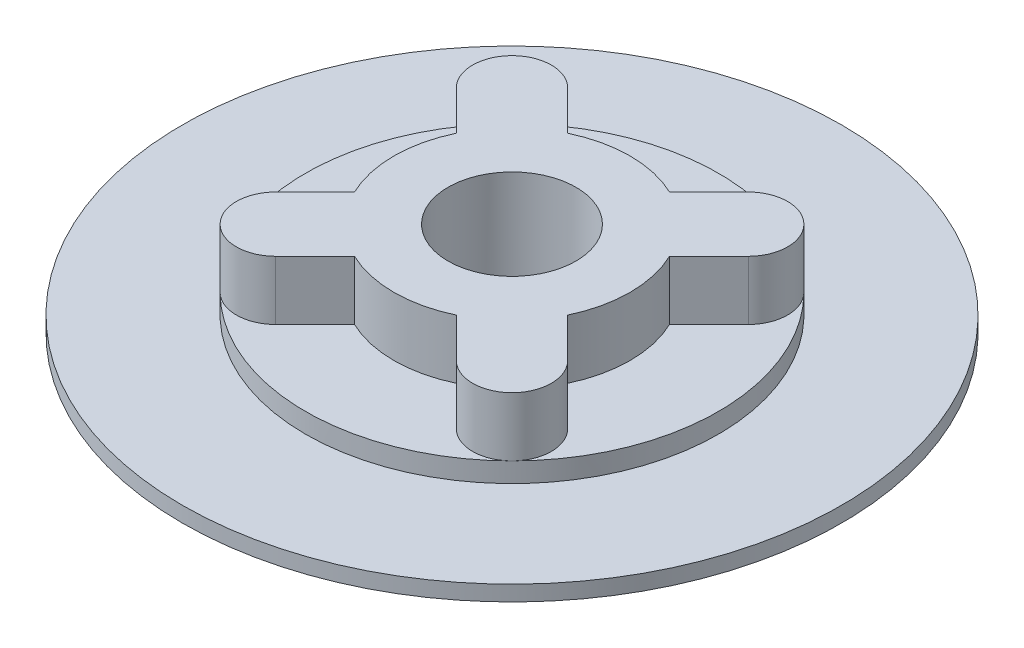
SolidWorks part; units mm, degrees
ref_plane "Front Plane" through (0, 0, 0) normal (0, 0, 1) x (1, 0, 0)
ref_plane "Top Plane" through (0, 0, 0) normal (0, 1, 0) x (1, 0, 0)
ref_plane "Right Plane" through (0, 0, 0) normal (1, 0, 0) x (0, 0, -1)
sketch "Sketch1" plane through (0, 0, 0) normal (0, 1, 0) x (1, 0, 0)
  circle A0 centre (0, 0) radius 53.1474
extrude "Boss-Extrude1" add sketch "Sketch1" along normal blind 2.4892
sketch "Sketch2" plane through (0, 2.4892, 0) normal (0, 1, 0) x (1, 0, 0)
  line L0 (-14.5599, 23.5401) -> (-8.2099, 17.1901)
  line L1 (-19.05, -19.05) -> (19.05, -19.05) construction
  line L2 (-19.05, -19.05) -> (-19.05, 19.05) construction
  line L3 (-19.05, 19.05) -> (19.05, 19.05) construction
  line L4 (19.05, -19.05) -> (19.05, 19.05) construction
  line L5 (-19.05, -19.05) -> (19.05, 19.05) construction
  line L6 (-19.05, 19.05) -> (19.05, -19.05) construction
  line L7 (-23.5401, 14.5599) -> (-17.1901, 8.2099)
  line L8 (23.5401, 14.5599) -> (17.1901, 8.2099)
  line L9 (14.5599, 23.5401) -> (8.2099, 17.1901)
  line L10 (14.5599, -23.5401) -> (8.2099, -17.1901)
  line L11 (23.5401, -14.5599) -> (17.1901, -8.2099)
  line L12 (-23.5401, -14.5599) -> (-17.1901, -8.2099)
  line L13 (-14.5599, -23.5401) -> (-8.2099, -17.1901)
  circle A0 centre (0, 0) radius 19.05
  circle A1 centre (-19.05, 19.05) radius 6.35
  circle A2 centre (19.05, 19.05) radius 6.35
  circle A3 centre (19.05, -19.05) radius 6.35
  circle A4 centre (-19.05, -19.05) radius 6.35
  point P33 (0, 0)
  dimension "D1" = 38.1
  dimension "D3" = 12.7
  dimension "D4" = 4
  dimension "D2" = 38.1
extrude "Boss-Extrude2" add sketch "Sketch2" along normal blind 12.7 contours A1 | A1 L7 A0 L0 | A0 | A2 | A2 L9 A0 L8 | A3 L11 A0 L10 | A3 | A4 | A4 L13 A0 L12 | A2 region at (-11.5382, 2.4892, -20.2118) region at (-19.05, 2.4892, -19.05) region at (0, 2.4892, 0) region at (11.5382, 2.4892, -20.2118) region at (19.05, 2.4892, -19.05) region at (-13.6237, 2.4892, 13.6237) region at (-19.05, 2.4892, 19.05) region at (20.2118, 2.4892, 11.5382) region at (19.05, 2.4892, 19.05)
sketch "Sketch3" plane through (0, 2.4892, 0) normal (0, 1, 0) x (1, 0, 0)
  circle A0 centre (0, 0) radius 33.2908
extrude "Boss-Extrude3" add sketch "Sketch3" along normal blind 3.175
sketch "Sketch4" plane through (0, 15.1892, 0) normal (0, 1, 0) x (1, 0, 0)
  circle A0 centre (0, 0) radius 10.3187
  dimension "D1" = 20.6375
extrude "Cut-Extrude1" cut sketch "Sketch4" against normal through all
sketch "Sketch5" plane through (0, 0, 0) normal (0, -1, 0) x (1, 0, 0)
  circle A0 centre (0, 0) radius 10.3187
  arc A1 (-23.5401, 23.5401) -> (-23.5401, -23.5401) centre (0, 0) ccw construction
  arc A2 (-23.5401, 23.5401) -> (-23.5401, -23.5401) centre (0, 0) ccw
  circle A3 centre (0, 0) radius 33.2908
  circle M1 centre (0, 0) radius 10.3187
extrude "Boss-Extrude4" add sketch "Sketch5" along normal blind 3.175 contours A2 A3 M1 region at (12.3795, 0, 29.8867)
